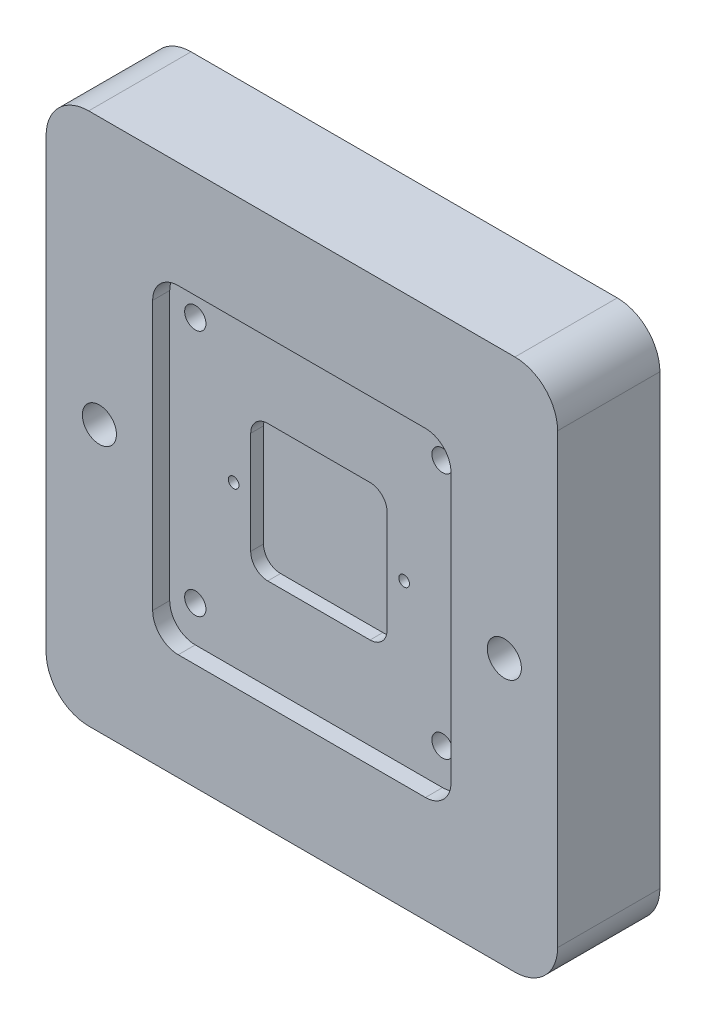
SolidWorks part; units mm, degrees
ref_plane "Front Plane" through (0, 0, 0) normal (0, 0, 1) x (1, 0, 0)
ref_plane "Top Plane" through (0, 0, 0) normal (0, 1, 0) x (1, 0, 0)
ref_plane "Right Plane" through (0, 0, 0) normal (1, 0, 0) x (0, 0, -1)
sketch "Sketch1" plane through (0, 0, 0) normal (0, 0, 1) x (1, 0, 0)
  line L0 (0, 62.5) -> (0, -62.5) construction
  line L1 (-50, 62.5) -> (50, 62.5)
  line L2 (-60, 52.5) -> (-60, -52.5)
  line L3 (-50, -62.5) -> (50, -62.5)
  line L4 (60, 52.5) -> (60, -52.5)
  line L5 (0, -62.5) -> (0, -37.5) construction
  line L6 (0, 37.5) -> (0, -37.5) construction
  line L7 (-29, 37.5) -> (29, 37.5)
  line L8 (-35, 31.5) -> (-35, -31.5)
  line L9 (-29, -37.5) -> (29, -37.5)
  line L10 (35, 31.5) -> (35, -31.5)
  line L11 (-35, 0) -> (-60, 0) construction
  line L12 (35, 0) -> (60, 0) construction
  arc A0 (50, 62.5) -> (60, 52.5) centre (50, 52.5) cw
  arc A1 (60, -52.5) -> (50, -62.5) centre (50, -52.5) cw
  arc A2 (-50, -62.5) -> (-60, -52.5) centre (-50, -52.5) cw
  arc A3 (-50, 62.5) -> (-60, 52.5) centre (-50, 52.5) ccw
  circle A4 centre (-47.5, 0) radius 4 construction
  circle A5 centre (47.5, 0) radius 4 construction
  arc A6 (-35, -31.5) -> (-29, -37.5) centre (-29, -31.5) ccw
  arc A7 (29, -37.5) -> (35, -31.5) centre (29, -31.5) ccw
  arc A8 (35, 31.5) -> (29, 37.5) centre (29, 31.5) ccw
  arc A9 (-29, 37.5) -> (-35, 31.5) centre (-29, 31.5) ccw
  point P31 (111.9206, -20.4692)
  point P32 (47.5, 0)
  point P39 (-47.5, 0)
  dimension "D1" = 10
  dimension "D2" = 8
  dimension "D3" = 6
  dimension "D4" = 70
  dimension "D5" = 75
  dimension "D6" = 25
extrude "Boss-Extrude1" add sketch "Sketch1" against normal blind 4
sketch "Sketch2" plane through (0, 0, -4) normal (0, 0, 1) x (1, 0, 0)
  line L8 (-50, -62.5) -> (50, -62.5) construction
  line L9 (60, 52.5) -> (60, -52.5) construction
  line L10 (-50, 62.5) -> (50, 62.5) construction
  line L11 (-60, 52.5) -> (-60, -52.5) construction
  line L12 (-50, -62.5) -> (50, -62.5)
  line L13 (60, 52.5) -> (60, -52.5)
  line L14 (-50, 62.5) -> (50, 62.5)
  line L15 (-60, 52.5) -> (-60, -52.5)
  arc A8 (50, -62.5) -> (60, -52.5) centre (50, -52.5) ccw construction
  arc A9 (60, 52.5) -> (50, 62.5) centre (50, 52.5) ccw construction
  arc A10 (-50, 62.5) -> (-60, 52.5) centre (-50, 52.5) ccw construction
  arc A11 (-60, -52.5) -> (-50, -62.5) centre (-50, -52.5) ccw construction
  arc A12 (50, -62.5) -> (60, -52.5) centre (50, -52.5) ccw
  arc A13 (60, 52.5) -> (50, 62.5) centre (50, 52.5) ccw
  arc A14 (-50, 62.5) -> (-60, 52.5) centre (-50, 52.5) ccw
  arc A15 (-60, -52.5) -> (-50, -62.5) centre (-50, -52.5) ccw
extrude "Boss-Extrude2" add sketch "Sketch2" against normal blind 20
sketch "Sketch3" plane through (0, 0, 0) normal (0, 0, 1) x (1, 0, 0)
  point P0 (-47.5, 0)
  point P3 (47.5, 0)
hole_wizard "Ø8.0mm Dowel Hole1" positions "Sketch3" profile "Sketch4" hole size "Ø8.0" standard "ANSI Metric"
sketch "Sketch4" plane through (-47.5, 0, 0) normal (1, 0, 0) x (0, -1, 0)
  line L0 (0, 0) -> (0, 20.4034)
  line L1 (0, 20.4034) -> (4, 18)
  line L2 (4, 18) -> (4, 0)
  line L5 (4, 0) -> (0, 0)
  line L10 (0, 20.4034) -> (-4, 18) construction
  line L11 (0, -6.35) -> (0, 107.95) construction
  dimension "Hole Dia." = 8
  dimension "Hole Depth" = 18
  dimension "Drill Angle" = 118
sketch "Sketch5" plane through (0, 0, -4) normal (0, 0, 1) x (1, 0, 0)
  line L0 (-29, 29) -> (29, -29) construction
  line L1 (-29, 29) -> (29, 29) construction
  line L2 (-29, 29) -> (-29, -29) construction
  line L3 (-29, -29) -> (29, -29) construction
  line L4 (29, 29) -> (29, -29) construction
  point P5 (-29, 29)
  point P7 (29, 29)
  point P8 (29, -29)
  point P9 (-29, -29)
  dimension "D1" = 58
sketch "Sketch6" plane through (0, 0, -4) normal (0, 0, 1) x (1, 0, 0)
  point P0 (-29, 29)
  point P3 (29, 29)
  point P6 (29, -29)
  point P9 (-29, -29)
hole_wizard "Tap Drill for M6x1.0 Tap1" positions "Sketch6" profile "Sketch7" hole size "M6x1.0" standard "ANSI Metric"
sketch "Sketch7" plane through (-29, 29, -4) normal (1, 0, 0) x (0, -1, 0)
  line L0 (0, 0) -> (0, 11.5022)
  line L1 (0, 11.5022) -> (2.5, 10)
  line L2 (2.5, 10) -> (2.5, 0)
  line L5 (2.5, 0) -> (0, 0)
  line L10 (0, 11.5022) -> (-2.5, 10) construction
  line L11 (0, -6.35) -> (0, 107.95) construction
  dimension "Hole Dia." = 5
  dimension "Hole Depth" = 10
  dimension "Drill Angle" = 118
sketch "Sketch8" [suppressed] plane through (0, 0, -4) normal (0, 0, 1) x (1, 0, 0)
  circle A0 centre (-29, 29) radius 2.75
  circle A1 centre (29, 29) radius 2.75
  circle A2 centre (29, -29) radius 2.75
  circle A3 centre (-29, -29) radius 2.75
  dimension "D1" = 5.5
extrude "Cut-Extrude1" [suppressed] cut sketch "Sketch8" against normal through all both and the other way through all
sketch "Sketch9" [suppressed] plane through (0, 0, -24) normal (0, 0, -1) x (-1, 0, 0)
  line L1 (-33.1, 26.6329) -> (-29, 24.2657)
  line L2 (-29, 24.2657) -> (-24.9, 26.6329)
  line L3 (-24.9, 26.6329) -> (-24.9, 31.3671)
  line L4 (-24.9, 31.3671) -> (-29, 33.7343)
  line L5 (-29, 33.7343) -> (-33.1, 31.3671)
  line L6 (-33.1, 31.3671) -> (-33.1, 26.6329)
  circle A0 centre (-29, 29) radius 4.1 construction
  dimension "D1" = 8.2
extrude "Cut-Extrude2" [suppressed] cut sketch "Sketch9" against normal blind 7 and the other way through all
pattern_sketch "Sketch-Pattern1" [suppressed] of bodies 106 driven by "Sketch5"
sketch "Sketch10" plane through (0, 0, 0) normal (0, 0, 1) x (1, 0, 0)
  circle A0 centre (47.5, 0) radius 4.05
  circle A1 centre (-47.5, 0) radius 4.05
  dimension "D1" = 8.1
extrude "Cut-Extrude3" [suppressed] cut sketch "Sketch10" against normal blind 20 and the other way through all
sketch "Sketch11" plane through (0, 0, -4) normal (0, 0, 1) x (1, 0, 0)
  line L1 (-12, 16) -> (12, 16)
  line L2 (-16, 12) -> (-16, -12)
  line L3 (-12, -16) -> (12, -16)
  line L4 (16, 12) -> (16, -12)
  circle A0 centre (0, 0) radius 16 construction
  arc A1 (-16, -12) -> (-12, -16) centre (-12, -12) ccw
  arc A2 (12, -16) -> (16, -12) centre (12, -12) ccw
  arc A3 (16, 12) -> (12, 16) centre (12, 12) ccw
  arc A4 (-12, 16) -> (-16, 12) centre (-12, 12) ccw
  dimension "D1" = 32
  dimension "D2" = 4
extrude "Cut-Extrude4" cut sketch "Sketch11" against normal blind 3
sketch "Sketch12" plane through (0, 0, -4) normal (0, 0, 1) x (1, 0, 0)
  point P11 (-20, 0)
  point P14 (20, 0)
sketch "smallinsertholelocations" plane through (0, 0, 0) normal (0, 0, 1) x (1, 0, 0)
  line L0 (-20, 0) -> (20, 0) construction
  point P3 (20, 0)
  point P5 (-20, 0)
  dimension "D1" = 40
sketch "Sketch16" [suppressed] plane through (0, 0, 0) normal (0, 0, 1) x (1, 0, 0)
  circle A0 centre (20, 0) radius 1.75
  circle A1 centre (-20, 0) radius 1.75
  dimension "D1" = 3.5
extrude "Cut-Extrude7" [suppressed] cut sketch "Sketch16" against normal through all
sketch "Sketch15" [suppressed] plane through (0, 0, -24) normal (0, 0, -1) x (-1, 0, 0)
  line L1 (-21.6743, -2.9) -> (-18.3257, -2.9)
  line L2 (-18.3257, -2.9) -> (-16.6514, 0)
  line L3 (-16.6514, 0) -> (-18.3257, 2.9)
  line L4 (-18.3257, 2.9) -> (-21.6743, 2.9)
  line L5 (-21.6743, 2.9) -> (-23.3486, 0)
  line L6 (-23.3486, 0) -> (-21.6743, -2.9)
  line L7 (21.6743, -2.9) -> (23.3486, 0)
  line L8 (23.3486, 0) -> (21.6743, 2.9)
  line L9 (21.6743, 2.9) -> (18.3257, 2.9)
  line L10 (18.3257, 2.9) -> (16.6514, 0)
  line L11 (16.6514, 0) -> (18.3257, -2.9)
  line L12 (18.3257, -2.9) -> (21.6743, -2.9)
  circle A0 centre (-20, 0) radius 2.9 construction
  circle A2 centre (20, 0) radius 2.9 construction
  circle A4 centre (-20, 0) radius 1.75 construction
  circle A5 centre (20, 0) radius 1.75 construction
  dimension "D1" = 5.8
extrude "Cut-Extrude6" [suppressed] cut sketch "Sketch15" against normal blind 3
hole_wizard "Tap Drill for M3 Tap1" positions "Sketch12" profile "Sketch13" hole size "M3" standard "DIN"
sketch "Sketch13" plane through (-20, 0, -4) normal (1, 0, 0) x (0, -1, 0)
  line L0 (0, 0) -> (0, 18.7511)
  line L1 (0, 18.7511) -> (1.25, 18)
  line L2 (1.25, 18) -> (1.25, 0)
  line L5 (1.25, 0) -> (0, 0)
  line L10 (0, 18.7511) -> (-1.25, 18) construction
  line L11 (0, -6.35) -> (0, 107.95) construction
  dimension "Hole Dia." = 2.5
  dimension "Hole Depth" = 18
  dimension "Drill Angle" = 118
